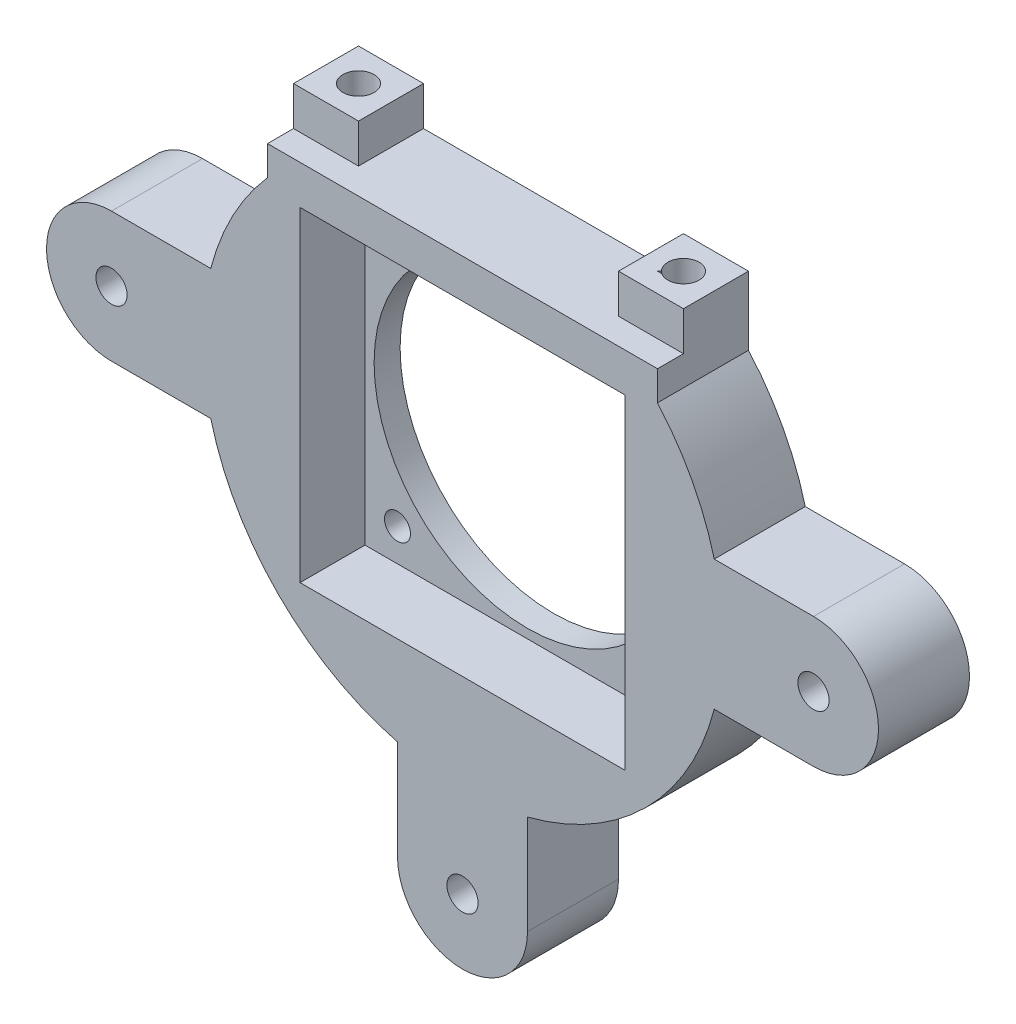
SolidWorks part; units mm, degrees
ref_plane "Front Plane" through (0, 0, 0) normal (1, 0, 0) x (0, 1, 0)
ref_plane "Top Plane" through (0, 0, 0) normal (0, 0, 1) x (0, 1, 0)
ref_plane "Right Plane" through (0, 0, 0) normal (0, 1, 0) x (-1, 0, 0)
sketch "Sketch2" plane through (0, 0, 0) normal (0, 0, 1) x (0, 1, 0)
  line L1 (-12.5, -12.5) -> (12.5, -12.5)
  line L2 (-12.5, -12.5) -> (-12.5, 12.5)
  line L3 (-12.5, 12.5) -> (12.5, 12.5)
  line L4 (12.5, -12.5) -> (12.5, 12.5)
  line L5 (-12.5, -12.5) -> (12.5, 12.5) construction
  line L6 (-12.5, 12.5) -> (12.5, -12.5) construction
  line L11 (-10, -10) -> (10, 10) construction
  line L12 (-10, 10) -> (10, -10) construction
  circle A0 centre (-10, 10) radius 1
  circle A1 centre (10, 10) radius 1
  circle A2 centre (10, -10) radius 1
  circle A3 centre (-10, -10) radius 1
  circle A4 centre (0, 0) radius 11.8
  circle A5 centre (0, 0) radius 20
  point P0 (0, 0)
  point P6 (0, 0)
  dimension "D1" = 25
  dimension "D2" = 25
  dimension "D3" = 20
extrude "Boss-Extrude1" add sketch "Sketch2" along normal blind 2 contours L1 L4 L3 L2 A4 A3 A2 A1 A0 | A5 L4 L1 L2 L3 region at (0, -12.1464, 0) region at (0, -19.4343, 0)
extrude "Boss-Extrude2" add sketch "Sketch2<3>" along normal blind 7 contours A5 L4 L1 L2 L3 region at (0, -19.4343, 0)
sketch "Sketch2<3>" plane through (0, 0, 0) normal (0, 0, 1) x (0, 1, 0) same geometry as "Sketch2"
sketch "Sketch4" plane through (0, 0, 0) normal (0, 0, -1) x (1, 0, 0)
  line L0 (0, 0) -> (27, 0)
  line L1 (12.5, -12.5) -> (-12.5, -12.5)
  line L2 (12.5, -12.5) -> (12.5, 12.5)
  line L3 (12.5, 12.5) -> (-12.5, 12.5)
  line L4 (-12.5, -12.5) -> (-12.5, 12.5)
  line L5 (12.5, -12.5) -> (-12.5, 12.5) construction
  line L6 (12.5, 12.5) -> (-12.5, -12.5) construction
  line L7 (27, 5) -> (12.5, 5)
  line L8 (27, -5) -> (12.5, -5)
  line L9 (5, -27) -> (5, -12.5)
  line L10 (-5, -27) -> (-5, -12.5)
  line L11 (-27, -5) -> (-12.5, -5)
  line L12 (-27, 5) -> (-12.5, 5)
  line L13 (-5, 27) -> (-5, 12.5)
  line L14 (5, 27) -> (5, 12.5)
  circle A0 centre (27, 0) radius 1.2
  circle A1 centre (27, 0) radius 5
  circle A2 centre (0, -27) radius 5
  circle A3 centre (0, -27) radius 1.2
  circle A4 centre (-27, 0) radius 5
  circle A5 centre (-27, 0) radius 1.2
  circle A6 centre (0, 27) radius 5
  circle A7 centre (0, 27) radius 1.2
  circle A8 centre (0, 0) radius 11.8 construction
  circle A9 centre (0, 0) radius 20
  point P0 (0, 0)
  circle M12 centre (0, 0) radius 20
  dimension "D3" = 4
  dimension "D1" = 25
  dimension "D2" = 25
extrude "Boss-Extrude3" add sketch "Sketch4" against normal up to surface (7 mm away) contours A2 A3 | A2 L9 L10 M12 | A4 L11 L12 M12 | A4 A5 | A6 A7 | A6 L13 L14 M12 | A1 A0 | A1 L0 L8 M12 | A1 L7 L0 M12 region at (21.6156, -3.0324, 0) region at (21.6156, 3.0324, 0) region at (23.5645, -3.4355, 0) region at (0, -21.6156, 0) region at (0, 21.6156, 0) region at (0, -22.1414, 0) region at (0, 31.8586, 0) region at (-21.6156, 0, 0) region at (-23.5645, -3.4355, 0) up to face at (0, 0, 7)
sketch "Sketch5" plane through (0, 0, 7) normal (0, 0, 1) x (1, 0, 0)
  line L0 (-12.5, 12.5) -> (-12.5, 15.5)
  line L2 (-12.5, 15.5) -> (12.5, 15.5)
  line L3 (-12.5, 15.5) -> (-12.5, 32.7453)
  line L4 (-12.5, 32.7453) -> (12.5, 32.7453)
  line L5 (12.5, 15.5) -> (12.5, 32.7453)
  arc M5 (19.3649, 5) -> (5, 19.3649) centre (0, 0) ccw
  line M6 (5, 19.3649) -> (5, 27)
  arc M7 (5, 27) -> (-5, 27) centre (0, 27) ccw
  line M8 (-5, 27) -> (-5, 19.3649)
  arc M9 (-5, 19.3649) -> (-19.3649, 5) centre (0, 0) ccw
  circle M24 centre (0, 27) radius 1.2
extrude "Cut-Extrude8" cut sketch "Sketch5" against normal blind 7 contours L2 L5 L3 M5 M6 M7 M8 M9 M24 region at (0, 21.9658, 7)
sketch "Sketch8" plane through (0, 15.5, 0) normal (0, 1, 0) x (-1, 0, 0)
  line L0 (-12.5, 3.5) -> (12.5, 3.5)
  line L1 (-12.5, 0) -> (-12.5, 7) construction
  line L2 (12.5, 0) -> (12.5, 7) construction
  line L3 (-12.5, 7) -> (-19.3649, 7) construction
  line L4 (15, 0) -> (-15, 0)
  line L5 (15, 0) -> (15, 7)
  line L6 (15, 7) -> (-15, 7)
  line L7 (-15, 0) -> (-15, 7)
  line L8 (15, 0) -> (-15, 7) construction
  line L9 (15, 7) -> (-15, 0) construction
  line L10 (-15, 0) -> (-10, 5)
  line L11 (-15, 0) -> (-10, 0)
  line L12 (-15, 0) -> (-15, 5)
  line L13 (-15, 5) -> (-10, 5)
  line L14 (-10, 0) -> (-10, 5)
  line L15 (0, 3.5) -> (0, 0.4191)
  line L16 (15, 5) -> (10, 5)
  line L17 (10, 0) -> (10, 5)
  line L18 (15, 0) -> (10, 0)
  line L19 (15, 0) -> (15, 5)
  circle A0 centre (-12.5, 2.5) radius 1.2
  circle A1 centre (12.5, 2.5) radius 1.2
  point P6 (0, 3.5)
  line M11 (-12.5, 7) -> (-12.5, 0)
  line M12 (-12.5, 0) -> (12.5, 0)
  line M13 (12.5, 0) -> (12.5, 7)
  dimension "D1" = 30
  dimension "D2" = 5
  dimension "D3" = 5
extrude "Boss-Extrude5" add sketch "Sketch8" against normal blind 2.5 contours L4 L5 L6 L7
sketch "Sketch9" plane through (0, 0, 7) normal (0, 0, 1) x (1, 0, 0)
  line L1 (15, 15.5) -> (-15, 15.5)
  line L2 (15, 15.5) -> (15, 16.9721)
  line L3 (15, 16.9721) -> (-15, 16.9721)
  line L4 (-15, 15.5) -> (-15, 16.9721)
extrude "Cut-Extrude9" cut sketch "Sketch9" against normal blind 12.5
extrude "Boss-Extrude6" add sketch "Sketch8<5>" along normal blind 3 contours A0 L14 L0 L10 M11 M12 | A0 L10 L4 M11 | A0 L13 L7 L10 M11 | A0 L0 L10 L13 M11 | L0 L14 L10 | A1 L0 L17 M13 M12 | L0 A1 L16 L17 M13 | A1 L4 L5 L16 M13 region at (11.5474, 15.5, 4.3847) region at (14.0677, 15.5, 3.1253) region at (10.5, 15.5, 4) region at (11.0065, 15.5, 1.5099) region at (13.4515, 15.5, 0.6242) region at (-11.2254, 15.5, 4.2665) region at (-11.009, 15.5, 1.5172) region at (-13.9136, 15.5, 2.5)
sketch "Sketch8<5>" plane through (0, 15.5, 0) normal (0, 1, 0) x (-1, 0, 0) same geometry as "Sketch8"
